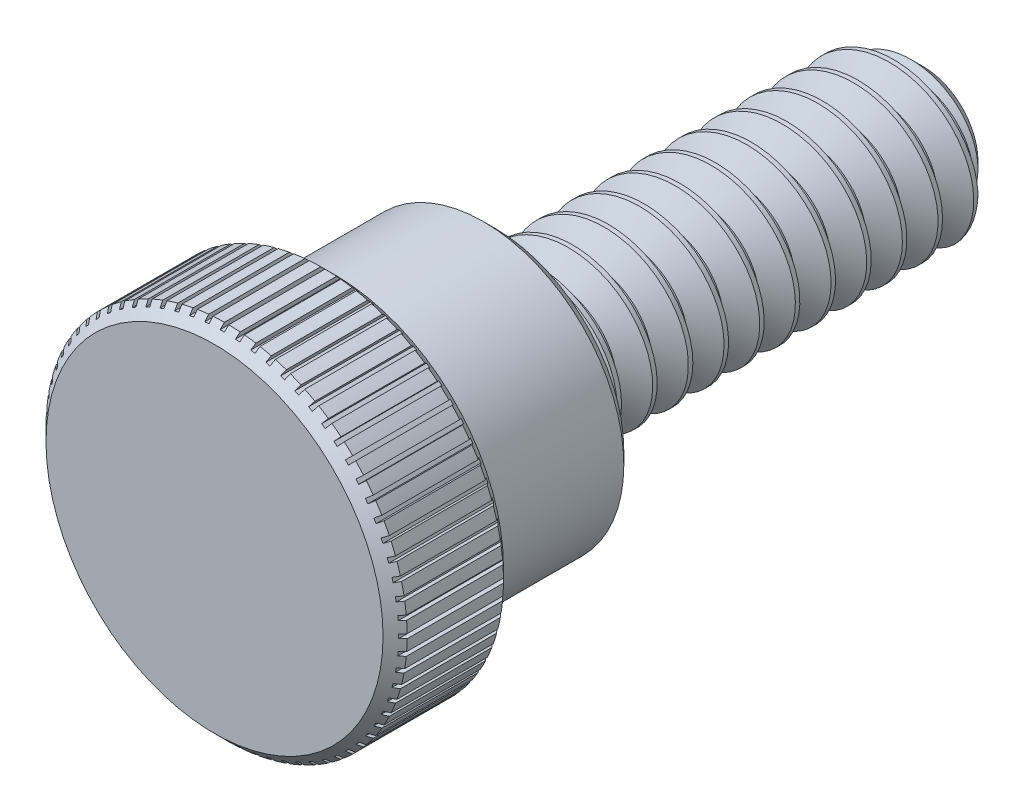
SolidWorks part; units mm, degrees
ref_plane "Front" through (0, 0, 0) normal (0, 0, 1) x (1, 0, 0)
ref_plane "Top" through (0, 0, 0) normal (0, 1, 0) x (1, 0, 0)
ref_plane "Right" through (0, 0, 0) normal (1, 0, 0) x (0, 0, -1)
sketch "Sketch20" plane through (0, 0, 0) normal (1, 0, 0) x (0, 0, -1)
  line L0 (0, 0) -> (12.7, 0) construction
  line L1 (12.7, 2.413) -> (12.7, -2.413) construction
  line L2 (-4.7625, 5.3578) -> (-4.7625, -5.3578) construction
  line L3 (-8.3344, 5.3578) -> (-8.3344, -5.3578) construction
  line L4 (0, 4.1672) -> (0, -4.1672) construction
  point P9 (7.9375, -2.413)
  point P11 (-4.7625, 0)
  point P14 (0, 0)
  dimension "D1" = 4.826
  dimension "D2" = 12.7
  dimension "D3" = 4.7625
  dimension "Head Height" = 3.5719
  dimension "Shoulder Diameter" = 8.3344
  dimension "Shoulder Length" = 4.7625
  dimension "Head Diameter" = 10.7156
sketch "Sketch1" plane through (0, 0, 0) normal (0, 0, 1) x (1, 0, 0)
  circle A0 centre (0, 0) radius 2.413
  dimension "dia" = 4.826
extrude "Extrude1" add sketch "Sketch1" against normal blind 12.7
chamfer "Chamfer2" distance 0.7937 angle 45 1 edges at (2.413, 0, -12.7)
sketch "Sketch15" plane through (0, 0, -12.7) normal (0, 0, -1) x (-1, 0, 0)
  circle A0 centre (0, 0) radius 2.413 construction
  circle A2 centre (0, 0) radius 2.413
curve "Helix/Spiral1" pitch 1.0583 height 13.7583 turns 13 parameters "pitch"=1.0583
sketch "Sketch14" plane through (0, 0, 0) normal (1, 0, 0) x (0, 0, -1)
  line L0 (12.7, 2.413) -> (13.626, 2.413)
  line L1 (13.626, 2.413) -> (13.2292, 1.7256)
  line L2 (13.2292, 1.7256) -> (13.0969, 1.7256)
  line L3 (13.0969, 1.7256) -> (12.7, 2.413)
  line L4 (12.8984, 2.0693) -> (13.4276, 2.0693) construction
  line L5 (12.7, -2.413) -> (12.7, 2.413) construction
  dimension "D1" = 0.1323
  dimension "D2" = 0.5292
  dimension "D3" = 60
sweep "Cut-Sweep1" cut profiles "Sketch14" path "Helix/Spiral1"
sketch "Sketch27" plane through (0, 0, 0) normal (0, 0, 1) x (1, 0, 0)
  circle A0 centre (0, 0) radius 4.1672
extrude "Boss-Extrude4" add sketch "Sketch27" along normal up to vertex (4.7625 mm away) up to point (0, 0, 4.7625)
sketch "Sketch21" plane through (0, 0, 4.7625) normal (0, 0, 1) x (1, 0, 0)
  line L0 (-5.3578, 0) -> (5.3578, 0) construction
  circle A0 centre (0, 0) radius 5.3578
extrude "Boss-Extrude1" add sketch "Sketch21" along normal up to vertex (3.5719 mm away) up to point (0, -5.3578, 8.3344)
chamfer "Chamfer3" distance 0.3572 angle 45 3 edges at (5.3578, 0, 4.7625) (5.3578, 0, 8.3344) (4.1672, 0, 0)
fillet "Fillet1" radius 0.3572 1 edges at (4.1672, 0, 4.7625)
ref_plane "Plane1" through (0, 5.3578, 0) normal (0, 1, 0) x (-1, 0, 0)
sketch "Sketch22" plane through (0, 5.3578, 0) normal (0, 1, 0) x (-1, 0, 0)
  line L0 (0, 8.3344) -> (0, 4.7625) construction
  line L1 (-0.0635, 8.3344) -> (0.0635, 8.3344)
  line L3 (-0.0635, 8.3344) -> (-0.0635, 4.7625)
  line L4 (-0.0635, 4.7625) -> (0.0635, 4.7625)
  line L7 (0.0635, 8.3344) -> (0.0635, 4.7625)
  dimension "D1" = 0.127
extrude "Cut-Extrude1" cut sketch "Sketch22" against normal offset from surface (0.1274 mm away) 0.127
pattern_circular "CirPattern1" count 72 over 360 about axis through (0, 0, 0) along (0, 0, 1) of "Cut-Extrude1"
equation "\"D3@Helix/Spiral1\" = \"Lg@Extrude1\"+\"pitch@Helix/Spiral1\""
equation "\"D1@Sketch14\" = \"pitch@Helix/Spiral1\" * .125"
equation "\"D2@Sketch14\" = \"pitch@Helix/Spiral1\" * .5"
equation "\"D1@Chamfer2\" = \"pitch@Helix/Spiral1\" * .75"
equation "\"D1@Sketch20\" = \"dia@Sketch1\""
equation "\"D2@Sketch20\" = \"Lg@Extrude1\""
equation "\"D1@Chamfer3\" =\"Head Height@Sketch20\"/10"
equation "\"D3@Sketch20\" = \"pitch@Helix/Spiral1\"*4.50"
equation "\"D1@Fillet1\" = \"D1@Chamfer3\""
